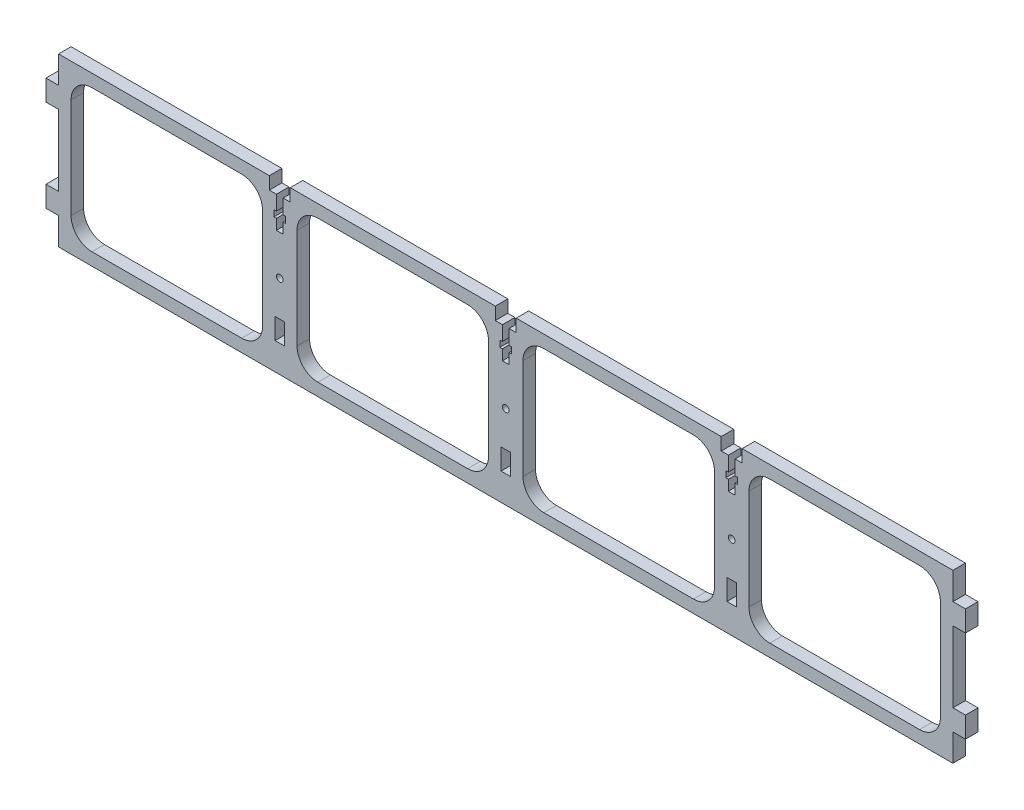
SolidWorks part; units mm, degrees
ref_plane "Front Plane" through (0, 0, 0) normal (0, 0, 1) x (1, 0, 0)
ref_plane "Top Plane" through (0, 0, 0) normal (0, 1, 0) x (1, 0, 0)
ref_plane "Right Plane" through (0, 0, 0) normal (1, 0, 0) x (0, 0, -1)
sketch "Sketch1" plane through (0, 0, 0) normal (0, 0, 1) x (1, 0, 0)
  line L1 (-214, -40) -> (214, -40)
  line L2 (-214, -40) -> (-214, 40)
  line L3 (-214, 40) -> (214, 40)
  line L4 (214, -40) -> (214, 40)
  line L5 (-214, -40) -> (214, 40) construction
  line L6 (-214, 40) -> (214, -40) construction
  point P0 (0, 0)
  dimension "D1" = 428
  dimension "D2" = 80
extrude "Boss-Extrude1" add sketch "Sketch1" along normal blind 6
sketch "Sketch2" plane through (0, 0, 6) normal (0, 0, 1) x (1, 0, 0)
  line L0 (-116.375, -40) -> (-116.375, -27) construction
  line L1 (-208, 40) -> (-208, -40) construction
  line L2 (-214, -34) -> (214, -34) construction
  line L3 (-214, -40) -> (214, -40) construction
  line L8 (214, -40) -> (214, 40)
  line L9 (214, 40) -> (-214, 40)
  line L10 (-214, 40) -> (-214, -40)
  line L11 (-214, -40) -> (214, -40)
  line L12 (214, -40) -> (214, 40) construction
  line L13 (214, 40) -> (-214, 40)
  line L14 (-214, 40) -> (-214, -40) construction
  line L15 (-208, -40) -> (214, -40) construction
  line L16 (-110.375, -40) -> (-110.375, -27) construction
  line L17 (-110.375, -40) -> (-110.375, -27) construction
  line L18 (-116.375, -24) -> (-116.375, 24)
  line L19 (-198, -34) -> (-126.375, -34)
  line L20 (-208, 24) -> (-208, -24)
  line L21 (-126.375, 34) -> (-198, 34)
  arc A0 (-198, 34) -> (-208, 24) centre (-198, 24) ccw
  arc A1 (-126.375, 34) -> (-116.375, 24) centre (-126.375, 24) cw
  arc A2 (-116.375, -24) -> (-126.375, -34) centre (-126.375, -24) cw
  arc A3 (-198, -34) -> (-208, -24) centre (-198, -24) cw
  dimension "D6" = 10
  dimension "D5" = 6
  dimension "D1" = 0
  dimension "D2" = 6
  dimension "D3" = 6
  dimension "D4" = 6
extrude "Cut-Extrude1" cut sketch "Sketch2" against normal up to next contours L18 L21 L20 L19 region at (-162.1875, 0, 6)
pattern_linear "LPattern1" count 4 spacing 108.125 along (1, 0, 0) of "Cut-Extrude1"
sketch "Sketch3" plane through (0, 0, 0) normal (0, 0, -1) x (-1, 0, 0)
  line L8 (-110.375, -27) -> (-110.375, -17) construction
  line L9 (-110.375, -17) -> (-105.875, -17) construction
  line L11 (-105.875, -27) -> (-110.375, -27) construction
  line L24 (-110.375, -27) -> (-110.375, -17)
  line L25 (-110.375, -17) -> (-105.875, -17)
  line L26 (-105.875, -17) -> (-105.875, -27)
  line L27 (-105.875, -27) -> (-110.375, -27)
  line L44 (-2.25, -27) -> (-2.25, -17) construction
  line L45 (-2.25, -17) -> (2.25, -17) construction
  line L46 (2.25, -17) -> (2.25, -27) construction
  line L47 (2.25, -27) -> (-2.25, -27) construction
  line L52 (-2.25, -27) -> (-2.25, -17)
  line L53 (-2.25, -17) -> (2.25, -17)
  line L54 (2.25, -17) -> (2.25, -27)
  line L55 (2.25, -27) -> (-2.25, -27)
  line L60 (105.875, -27) -> (105.875, -17) construction
  line L61 (105.875, -17) -> (110.375, -17) construction
  line L62 (110.375, -17) -> (110.375, -27) construction
  line L63 (110.375, -27) -> (105.875, -27) construction
  line L68 (105.875, -27) -> (105.875, -17)
  line L69 (105.875, -17) -> (110.375, -17)
  line L70 (110.375, -17) -> (110.375, -27)
  line L71 (110.375, -27) -> (105.875, -27)
  circle A3 centre (108.125, 0) radius 1.6 construction
  circle A4 centre (0, 0) radius 1.6 construction
  circle A5 centre (-108.125, 0) radius 1.6 construction
  circle A6 centre (108.125, 0) radius 1.6
  circle A7 centre (0, 0) radius 1.6
  circle A8 centre (-108.125, 0) radius 1.6
extrude "Cut-Extrude2" cut sketch "Sketch3" against normal through all
sketch "Sketch4" plane through (0, 0, 0) normal (0, 0, -1) x (-1, 0, 0)
  line L0 (-111.5, 17) -> (-214, 17) construction
  line L1 (-214, -40) -> (-214, 40) construction
  line L2 (-108.5, 0) -> (-214, 0) construction
  line L3 (-220, 21.3321) -> (-220, 40) construction
  line L4 (-214, 17) -> (-220, 17)
  line L5 (-214, 17) -> (-214, 27)
  line L6 (-214, 27) -> (-220, 27)
  line L7 (-220, 17) -> (-220, 27)
  line L9 (-220, -17) -> (-220, -27)
  line L10 (-214, -27) -> (-220, -27)
  line L11 (-214, -17) -> (-214, -27)
  line L12 (-214, -17) -> (-220, -17)
  line L13 (0, 0) -> (0, 40) construction
  line L14 (-214, 40) -> (214, 40) construction
  line L15 (214, -17) -> (220, -17)
  line L16 (214, -17) -> (214, -27)
  line L17 (214, -27) -> (220, -27)
  line L18 (220, -17) -> (220, -27)
  line L19 (220, 17) -> (220, 27)
  line L20 (214, 27) -> (220, 27)
  line L21 (214, 17) -> (214, 27)
  line L22 (214, 17) -> (220, 17)
  point P13 (-108.5, -1)
  dimension "D1" = 34
  dimension "D2" = 10
extrude "Boss-Extrude2" add sketch "Sketch4" against normal blind 6
sketch "Sketch5" plane through (0, 40, 0) normal (0, 1, 0) x (1, 0, 0)
  line L0 (214, -6) -> (-214, -6) construction
  line L1 (-113.125, 0) -> (-103.125, 0)
  line L2 (-113.125, 0) -> (-113.125, -6)
  line L3 (-113.125, -6) -> (-103.125, -6)
  line L4 (-103.125, 0) -> (-103.125, -6)
  line L5 (-113.125, 0) -> (-103.125, -6) construction
  line L6 (-113.125, -6) -> (-103.125, 0) construction
  line L7 (-103.125, -6) -> (-103.125, 0) construction
  line L8 (5, -6) -> (5, 0) construction
  line L9 (-5, 0) -> (5, 0)
  line L10 (-5, 0) -> (-5, -6)
  line L11 (-5, -6) -> (5, -6)
  line L12 (5, 0) -> (5, -6)
  line L13 (-5, 0) -> (5, -6) construction
  line L14 (-5, -6) -> (5, 0) construction
  line L15 (113.125, -6) -> (113.125, 0) construction
  line L16 (103.125, 0) -> (113.125, 0)
  line L17 (103.125, 0) -> (103.125, -6)
  line L18 (103.125, -6) -> (113.125, -6)
  line L19 (113.125, 0) -> (113.125, -6)
  line L20 (103.125, 0) -> (113.125, -6) construction
  line L21 (103.125, -6) -> (113.125, 0) construction
  point P0 (-108.125, -3)
  point P10 (0, -3)
  point P18 (108.125, -3)
extrude "Cut-Extrude3" cut sketch "Sketch5" against normal blind 6
sketch "Sketch6" plane through (0, 0, 0) normal (0, 0, -1) x (-1, 0, 0)
  line L12 (-109.725, 34) -> (-109.725, 27)
  line L13 (-106.525, 34) -> (-109.725, 34)
  line L14 (-106.525, 27) -> (-106.525, 34)
  line L15 (-105.325, 27) -> (-106.525, 27)
  line L16 (-105.325, 24) -> (-105.325, 27)
  line L17 (-106.525, 24) -> (-105.325, 24)
  line L18 (-106.525, 19) -> (-106.525, 24)
  line L19 (-109.725, 19) -> (-106.525, 19)
  line L20 (-109.725, 24) -> (-109.725, 19)
  line L21 (-110.925, 24) -> (-109.725, 24)
  line L22 (-110.925, 27) -> (-110.925, 24)
  line L23 (-109.725, 27) -> (-110.925, 27)
  line L24 (-109.725, 34) -> (-109.725, 27)
  line L25 (-106.525, 34) -> (-109.725, 34)
  line L26 (-106.525, 27) -> (-106.525, 34)
  line L27 (-105.325, 27) -> (-106.525, 27)
  line L28 (-105.325, 24) -> (-105.325, 27)
  line L29 (-106.525, 24) -> (-105.325, 24)
  line L30 (-106.525, 19) -> (-106.525, 24)
  line L31 (-109.725, 19) -> (-106.525, 19)
  line L32 (-109.725, 24) -> (-109.725, 19)
  line L33 (-110.925, 24) -> (-109.725, 24)
  line L34 (-110.925, 27) -> (-110.925, 24)
  line L35 (-109.725, 27) -> (-110.925, 27)
  line L36 (-1.595, 27) -> (-2.795, 27)
  line L37 (-2.795, 27) -> (-2.795, 24)
  line L38 (-2.795, 24) -> (-1.595, 24)
  line L39 (-1.595, 24) -> (-1.595, 19)
  line L40 (-1.595, 19) -> (1.605, 19)
  line L41 (1.605, 19) -> (1.605, 24)
  line L42 (1.605, 24) -> (2.805, 24)
  line L43 (2.805, 24) -> (2.805, 27)
  line L44 (2.805, 27) -> (1.605, 27)
  line L45 (1.605, 27) -> (1.605, 34)
  line L46 (1.605, 34) -> (-1.595, 34)
  line L47 (-1.595, 34) -> (-1.595, 27)
  line L48 (-1.595, 27) -> (-2.795, 27)
  line L49 (-2.795, 27) -> (-2.795, 24)
  line L50 (-2.795, 24) -> (-1.595, 24)
  line L51 (-1.595, 24) -> (-1.595, 19)
  line L52 (-1.595, 19) -> (1.605, 19)
  line L53 (1.605, 19) -> (1.605, 24)
  line L54 (1.605, 24) -> (2.805, 24)
  line L55 (2.805, 24) -> (2.805, 27)
  line L56 (2.805, 27) -> (1.605, 27)
  line L57 (1.605, 27) -> (1.605, 34)
  line L58 (1.605, 34) -> (-1.595, 34)
  line L59 (-1.595, 34) -> (-1.595, 27)
  line L60 (106.535, 34) -> (106.535, 27)
  line L61 (109.735, 34) -> (106.535, 34)
  line L62 (109.735, 27) -> (109.735, 34)
  line L63 (110.935, 27) -> (109.735, 27)
  line L64 (110.935, 24) -> (110.935, 27)
  line L65 (109.735, 24) -> (110.935, 24)
  line L66 (109.735, 19) -> (109.735, 24)
  line L67 (106.535, 19) -> (109.735, 19)
  line L68 (106.535, 24) -> (106.535, 19)
  line L69 (105.335, 24) -> (106.535, 24)
  line L70 (105.335, 27) -> (105.335, 24)
  line L71 (106.535, 27) -> (105.335, 27)
  line L72 (106.535, 34) -> (106.535, 27)
  line L73 (109.735, 34) -> (106.535, 34)
  line L74 (109.735, 27) -> (109.735, 34)
  line L75 (110.935, 27) -> (109.735, 27)
  line L76 (110.935, 24) -> (110.935, 27)
  line L77 (109.735, 24) -> (110.935, 24)
  line L78 (109.735, 19) -> (109.735, 24)
  line L79 (106.535, 19) -> (109.735, 19)
  line L80 (106.535, 24) -> (106.535, 19)
  line L81 (105.335, 24) -> (106.535, 24)
  line L82 (105.335, 27) -> (105.335, 24)
  line L83 (106.535, 27) -> (105.335, 27)
  dimension "D1" = 0
  dimension "D2" = 0
  dimension "D3" = 0
extrude "Cut-Extrude4" cut sketch "Sketch6" against normal up to next
